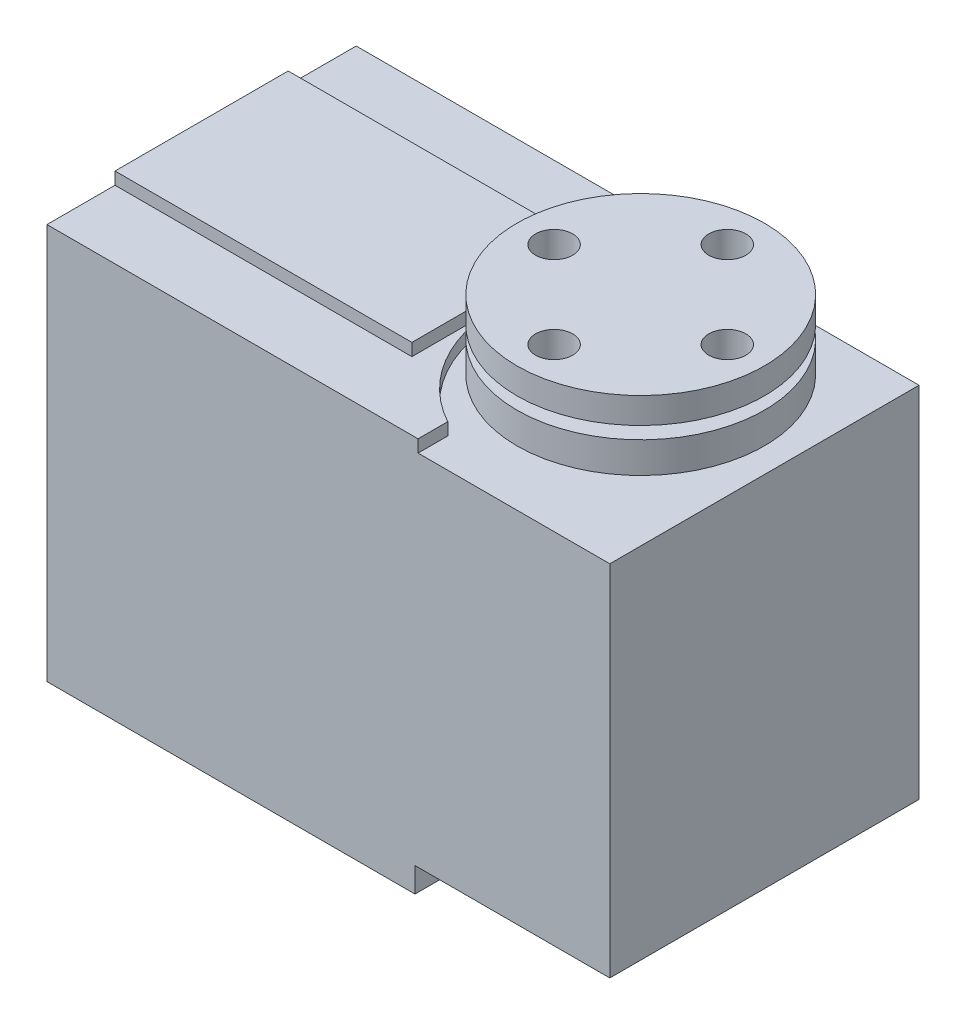
SolidWorks part; units mm, degrees
ref_plane "Front Plane" through (0, 0, 0) normal (0, 0, 1) x (1, 0, 0)
ref_plane "Top Plane" through (0, 0, 0) normal (0, 1, 0) x (1, 0, 0)
ref_plane "Right Plane" through (0, 0, 0) normal (1, 0, 0) x (0, 0, -1)
sketch "Main Body Sketch" plane through (0, 0, 0) normal (0, 1, 0) x (1, 0, 0)
  line L1 (-22.75, 12.5) -> (22.75, 12.5)
  line L2 (-22.75, 12.5) -> (-22.75, -12.5)
  line L3 (-22.75, -12.5) -> (22.75, -12.5)
  line L4 (22.75, 12.5) -> (22.75, -12.5)
  point P4 (0, 12.5)
  point P6 (-22.75, 0)
  dimension "D1" = 45.5
  dimension "D2" = 25
extrude "Main Body Extrusion" add sketch "Main Body Sketch" along normal blind 29
sketch "Sketch2" plane through (0, 29, 0) normal (0, 1, 0) x (1, 0, 0)
  line L0 (-22.75, 12.5) -> (-22.75, -12.5) construction
  line L1 (-22.75, 12.5) -> (7.25, 12.5)
  line L2 (-22.75, 12.5) -> (-22.75, -12.5)
  line L3 (-22.75, -12.5) -> (7.25, -12.5)
  line L4 (7.25, 12.5) -> (7.25, 10.0995)
  line L5 (7.25, -10.0995) -> (7.25, -12.5)
  line L6 (22.75, 12.5) -> (-22.75, 12.5) construction
  line L7 (22.75, -12.5) -> (22.75, 12.5) construction
  arc A1 (7.25, 10.0995) -> (7.25, -10.0995) centre (12.75, 0) ccw
  point P14 (22.75, 0)
  dimension "D1" = 11.5
  dimension "D2" = 30
  dimension "D3" = 10
extrude "Boss-Extrude3" add sketch "Sketch2" along normal blind 1
sketch "Sketch8" plane through (0, 30, 0) normal (0, 1, 0) x (1, 0, 0)
  line L0 (-22.75, 12.5) -> (-22.75, -12.5) construction
  line L1 (-22.75, 7) -> (1.25, 7)
  line L2 (-22.75, 7) -> (-22.75, -7)
  line L3 (-22.75, -7) -> (1.25, -7)
  line L4 (1.25, 7) -> (1.25, -7)
  arc A0 (7.25, 10.0995) -> (7.25, -10.0995) centre (12.75, 0) ccw construction
  point P6 (-22.75, 0)
  point P7 (1.25, 0)
  dimension "D1" = 14
extrude "Boss-Extrude8" add sketch "Sketch8" along normal blind 1
sketch "Sketch3" plane through (0, 29, 0) normal (0, 1, 0) x (1, 0, 0)
  line L0 (22.75, -12.5) -> (22.75, 12.5) construction
  circle A0 centre (12.75, 0) radius 2.25
  point P5 (22.75, 0)
  dimension "D2" = 4.5
  dimension "D1" = 10
extrude "Boss-Extrude4" add sketch "Sketch3" along normal blind 2
sketch "Sketch4" plane through (0, 0, 0) normal (0, -1, 0) x (1, 0, 0)
  line L0 (22.75, 12.5) -> (22.75, -12.5) construction
  line L1 (0, 12.5) -> (0, -12.5) construction
  line L2 (-22.75, 12.5) -> (22.75, 12.5) construction
  line L3 (22.75, -12.5) -> (-22.75, -12.5) construction
  circle A0 centre (12.5, 0) radius 3
  circle A1 centre (12.5, 0) radius 1.25
  point P4 (22.75, 0)
  dimension "D1" = 6
  dimension "D3" = 2.5
  dimension "D2" = 12.5
sketch "Sketch5" plane through (0, 0, 0) normal (0, -1, 0) x (1, 0, 0)
  line L0 (-22.75, -12.5) -> (-22.75, 12.5) construction
  line L1 (-22.75, 12.5) -> (-4, 12.5)
  line L2 (-22.75, 12.5) -> (-22.75, -12.5)
  line L3 (-22.75, -12.5) -> (-4, -12.5)
  line L4 (-4, 12.5) -> (-4, -12.5)
  line L5 (-22.75, 12.5) -> (22.75, 12.5) construction
  line L6 (1, 10) -> (1, 6.5)
  line L7 (-4, 12.5) -> (7, 12.5)
  line L8 (-4, 12.5) -> (-4, 10)
  line L9 (-4, 10) -> (1, 10)
  line L10 (7, 12.5) -> (7, 10)
  line L11 (1, 6.5) -> (3.5, 6.5)
  line L12 (3.5, 6.5) -> (7, 10)
  line L13 (-20.9143, 0) -> (8.4235, 0) construction
  line L14 (3.5, -6.5) -> (7, -10)
  line L15 (1, -6.5) -> (3.5, -6.5)
  line L16 (7, -12.5) -> (7, -10)
  line L17 (-4, -10) -> (1, -10)
  line L18 (-4, -12.5) -> (7, -12.5)
  line L19 (1, -10) -> (1, -6.5)
  line L21 (22.75, 12.5) -> (22.75, -12.5) construction
  point P6 (-22.75, 0)
  point P7 (-22.75, 0)
  line M7 (-22.75, -12.5) -> (22.75, -12.5)
  line M9 (22.75, 12.5) -> (-22.75, 12.5)
  dimension "D1" = 18.75
  dimension "D3" = 11
  dimension "D4" = 2.5
  dimension "D5" = 3.5
  dimension "D6" = 2.5
  dimension "D7" = 21.75
sketch "Sketch6" plane through (0, 31, 0) normal (0, 1, 0) x (1, 0, 0)
  circle A0 centre (12.75, 0) radius 10
  circle A1 centre (12.75, 0) radius 2.25 construction
  dimension "D1" = 20
extrude "Boss-Extrude7" add sketch "Sketch6" along normal blind 2.5
sketch "Sketch7" plane through (0, 33.5, 0) normal (0, 1, 0) x (1, 0, 0)
  line L0 (12.75, 0) -> (12.75, 7) construction
  line L1 (5.75, 0) -> (12.75, 0) construction
  circle A0 centre (12.75, 0) radius 10 construction
  circle A1 centre (12.75, 7) radius 1.5
  circle A2 centre (12.75, -7) radius 1.5
  circle A3 centre (5.75, 0) radius 1.5
  circle A4 centre (19.75, 0) radius 1.5
  dimension "D2" = 3
  dimension "D1" = 7
extrude "Cut-Extrude1" cut sketch "Sketch7" against normal blind 2
sketch "Sketch10" plane through (0, 33.5, 0) normal (0, 1, 0) x (1, 0, 0)
  circle A0 centre (12.75, 0) radius 2.25
  circle A1 centre (12.75, 0) radius 10 construction
  dimension "D1" = 4.5
extrude "Boss-Extrude12" add sketch "Sketch10" along normal blind 1
sketch "Sketch11" plane through (0, 34.5, 0) normal (0, 1, 0) x (1, 0, 0)
  circle A0 centre (12.75, 0) radius 10
  circle A1 centre (12.75, 0) radius 2.25 construction
  dimension "D1" = 20
extrude "Boss-Extrude13" add sketch "Sketch11" along normal blind 2.1
sketch "Sketch13" plane through (0, 36.6, 0) normal (0, 1, 0) x (1, 0, 0)
  line L0 (12.75, 0) -> (5.75, 0) construction
  line L1 (12.75, 7) -> (12.75, 0) construction
  circle A0 centre (12.75, 0) radius 10 construction
  circle A1 centre (12.75, 7) radius 1.5
  circle A2 centre (5.75, 0) radius 1.5
  circle A3 centre (12.75, -7) radius 1.5
  circle A4 centre (19.75, 0) radius 1.5
  dimension "D1" = 3
  dimension "D2" = 7
extrude "Cut-Extrude3" cut sketch "Sketch13" against normal blind 2.1
extrude "Boss-Extrude9" add sketch "Sketch5" along normal blind 2 contours L11 L12 L10 L4 L9 L6 M9 | L13 L2 L4 M7 | L19 L17 L4 L16 L14 L15 M7 region at (-13.375, 0, 0) region at (2.1126, 0, 10.2812) region at (2.1126, 0, -10.2812)
sketch "Sketch9" plane through (0, 0, 0) normal (0, -1, 0) x (1, 0, 0)
  line L1 (1, 10) -> (-4, 10)
  line L2 (1, 10) -> (1, -10)
  line L3 (1, -10) -> (-4, -10)
  line L4 (-4, 10) -> (-4, -10)
extrude "Cut-Extrude2" cut sketch "Sketch9" against normal blind 5
extrude "Boss-Extrude10" add sketch "Sketch4" along normal blind 4.1
sketch "Sketch14" plane through (0, -2, 0) normal (0, -1, 0) x (1, 0, 0)
  line L0 (-4, 10) -> (-4, -10) construction
  line L1 (-4, 8.9073) -> (-17.5, 8.9073)
  line L2 (-4, 8.9073) -> (-4, -8.9488)
  line L3 (-4, -8.9488) -> (-17.5, -8.9488)
  line L4 (-17.5, 8.9073) -> (-17.5, -8.9488)
  dimension "D1" = 13.5
extrude "Boss-Extrude14" add sketch "Sketch14" along normal blind 2
